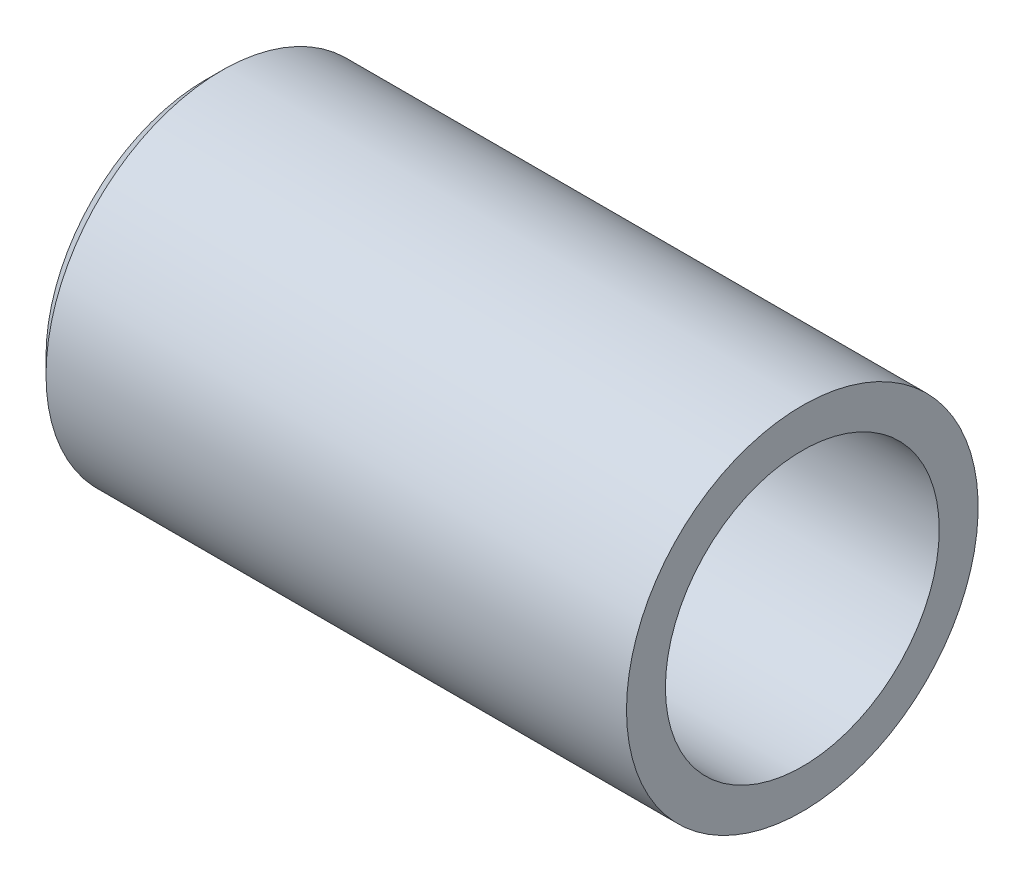
SolidWorks part; units mm, degrees
material "Nylon 6/10"
ref_plane "Front Plane" through (0, 0, 0) normal (0, 0, 1) x (1, 0, 0)
ref_plane "Top Plane" through (0, 0, 0) normal (0, 1, 0) x (1, 0, 0)
ref_plane "Right Plane" through (0, 0, 0) normal (1, 0, 0) x (0, 0, -1)
sketch "Sketch1" plane through (0, 0, 0) normal (0, 0, 1) x (1, 0, 0)
  line L0 (0, 0) -> (22.1407, 0) construction
  line L1 (6.7033, 5.4227) -> (24.6062, 5.4227)
  line L3 (6.2063, 4.2228) -> (24.6062, 4.2228)
  line L4 (24.6062, 5.4227) -> (24.6062, 4.2228)
  line L5 (24.6062, 11.1125) -> (24.6062, -11.1125) construction
  line L6 (63.2354, 3.9688) -> (-48.4378, 3.9688) construction
  line L7 (6.2063, -4.1672) -> (6.2063, 4.1672) construction
  line L8 (6.2063, 4.2228) -> (6.2063, 4.9257)
  line L9 (6.2063, 4.9257) -> (6.7033, 5.4227)
  dimension "D4" = 45
  dimension "D2" = 1.2
  dimension "D1" = 0.254
revolve "Revolve1" add sketch "Sketch1" angle 360 about L0
equation "\"D2@Sketch1\"=1.2mm"
